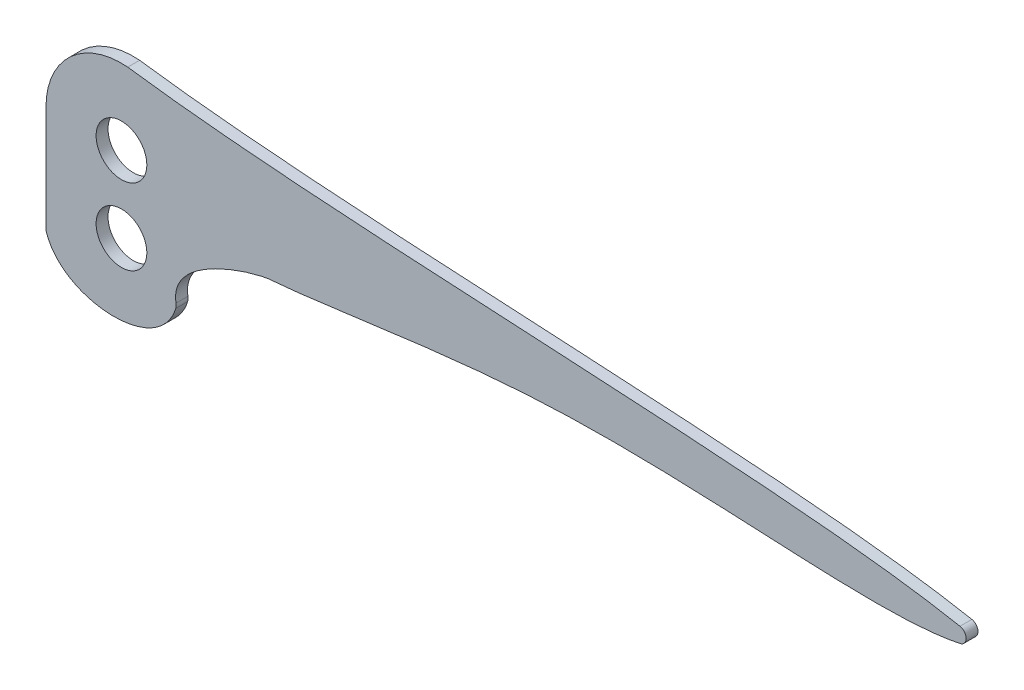
SolidWorks part; units mm, degrees
ref_plane "Front Plane" through (0, 0, 0) normal (0, 0, 1) x (1, 0, 0)
ref_plane "Top Plane" through (0, 0, 0) normal (0, 1, 0) x (1, 0, 0)
ref_plane "Right Plane" through (0, 0, 0) normal (1, 0, 0) x (0, 0, -1)
sketch "Sketch1" plane through (0, 0, 0) normal (0, 0, 1) x (1, 0, 0)
  line L0 (0, 0) -> (0, -25.4) construction
  line L1 (-25.1919, 0) -> (-25.1919, -35.2154)
  arc A1 (279.8894, 2.3729) -> (279.9348, -2.6026) centre (279.4, -0.1195) cw
  arc A2 (2.0902, 25.105) -> (-25.1919, 0) centre (0, 0) ccw
  circle A5 centre (0, -25.4) radius 8.4667
  circle A6 centre (0, 0) radius 8.4667
  arc A8 (18.2122, -35.0564) -> (18.1176, -36.6407) centre (14.8556, -35.6511) cw
  arc A9 (-25.1919, -35.2154) -> (-25.0041, -36.3312) centre (-21.783, -35.2154) ccw
  spline S0 degree 3 poles (2.0902, 25.105) (29.3726, 21.3189) (128.0417, 14.5406) (239.5484, 10.2935) (279.8894, 2.3729) knots 0.008543 0.008543 0.008543 0.008543 0.340595 0.941395 0.941395 0.941395 0.941395
  spline S1 degree 3 poles (50.3146, -12.4878) (67.829, -11.2174) (162.8512, 6.0974) (250.0383, -9.0418) (279.9348, -2.6026) knots 0.235846 0.235846 0.235846 0.235846 0.495201 0.941477 0.941477 0.941477 0.941477
  spline S2 degree 3 poles (18.2122, -35.0564) (15.7223, -21.0033) (45.0837, -12.5774) (50.3146, -12.4878) knots 0.243689 0.243689 0.243689 0.243689 1 1 1 1
  spline S3 degree 3 poles (-25.0041, -36.3312) (-24.3022, -38.3573) (-17.5003, -49.4729) (6.4866, -52.353) (16.8283, -40.8908) (18.1176, -36.6407) knots 0.011286 0.011286 0.011286 0.011286 0.130988 0.750185 0.983992 0.983992 0.983992 0.983992
  point P3 (76.2, 0)
  dimension "D1" = 3.4089
  dimension "D2" = 2.54
  dimension "D3" = 16.9333
  dimension "D6" = 279.4
extrude "Boss-Extrude1" add sketch "Sketch1" along normal blind 3.9688 contours S1 A1 S0 region at (77.9982, -1.3579, 0)
scale "Scale1" scale about centroid uniform scaling yes scale factor 0.75
